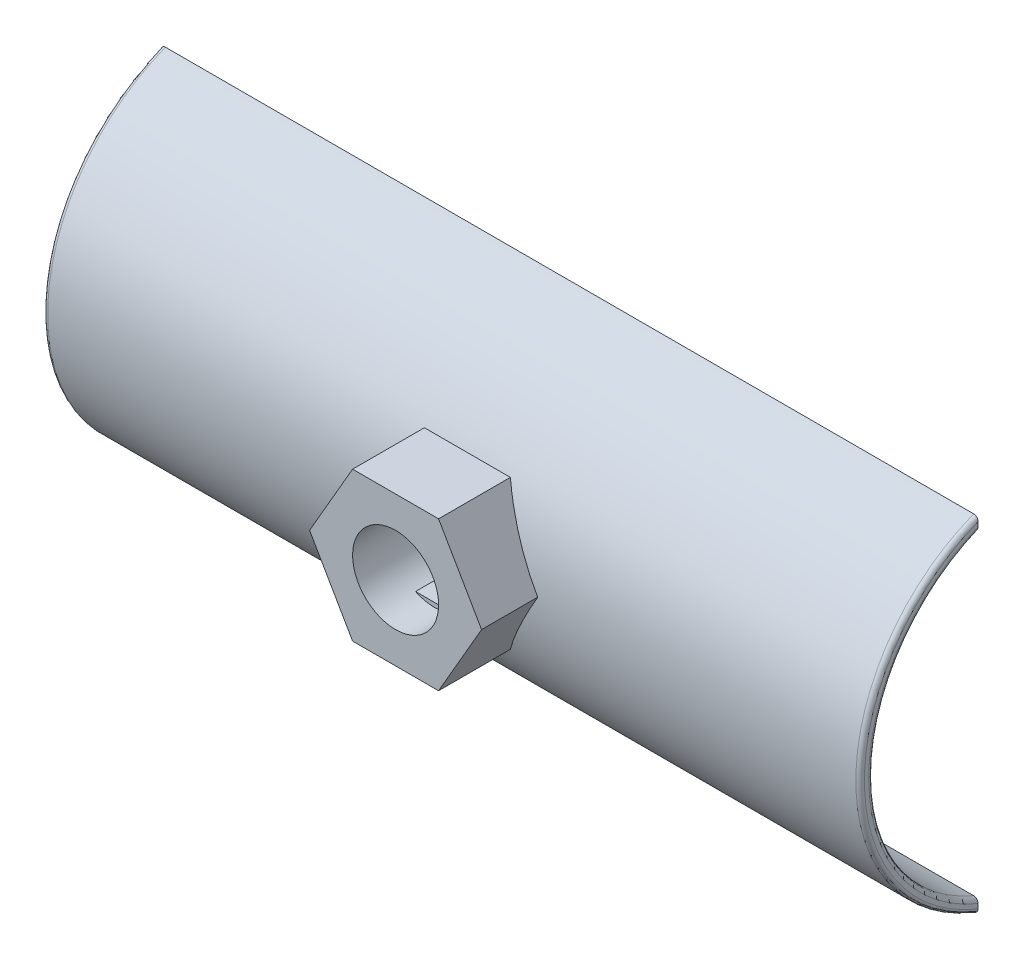
SolidWorks part; units mm, degrees
ref_plane "Front Plane" through (0, 0, 0) normal (0, 0, 1) x (1, 0, 0)
ref_plane "Top Plane" through (0, 0, 0) normal (0, 1, 0) x (1, 0, 0)
ref_plane "Right Plane" through (0, 0, 0) normal (1, 0, 0) x (0, 0, -1)
sketch "Sketch1" plane through (0, 0, 0) normal (0, 0, 1) x (1, 0, 0)
  line L0 (10, -17.3205) -> (20, 0)
  line L1 (20, 0) -> (10, 17.3205)
  line L2 (10, 17.3205) -> (-10, 17.3205)
  line L3 (-10, 17.3205) -> (-20, 0)
  line L4 (-20, 0) -> (-10, -17.3205)
  line L5 (-10, -17.3205) -> (10, -17.3205)
  circle A0 centre (0, 0) radius 17.3205 construction
  dimension "D1" = 20
extrude "Boss-Extrude1" add sketch "Sketch1" along normal blind 20
sketch "Sketch3" plane through (0, 0, 0) normal (0, 0, -1) x (-1, 0, 0)
  line L0 (0, 0) -> (0, 10) construction
  line L1 (0, 0) -> (10, 0) construction
  line L2 (-4.3589, 9) -> (4.3589, 9)
  line L3 (-4.3589, -9) -> (4.3589, -9)
  circle A0 centre (0, 0) radius 10
  dimension "D1" = 9
extrude "Cut-Extrude1" cut sketch "Sketch3" against normal blind 11 contours L2 A0 L3 region at (0, 0, 0)
sketch "Sketch4" plane through (0, 0, 11) normal (0, 0, -1) x (-1, 0, 0)
  circle A0 centre (0, 0) radius 10
extrude "Cut-Extrude2" cut sketch "Sketch4" against normal blind 11
sketch "Sketch5" plane through (0, 0, 0) normal (1, 0, 0) x (0, 0, -1)
  line L0 (0, 0) -> (76.0555, 0) construction
  line L2 (-20, -17.3205) -> (0, -17.3205) construction
  line L5 (20.4789, 40.0795) -> (20.4789, 36.8425)
  line L6 (20.4789, -36.8425) -> (20.4789, -40.0795)
  arc A2 (20.4789, 36.8425) -> (20.4789, -36.8425) centre (36.0555, 0) ccw
  arc A3 (20.4789, 40.0795) -> (20.4789, -40.0795) centre (36.0555, 0) ccw
extrude "Boss-Extrude2" add sketch "Sketch5" along normal blind 95 and the other way blind 95
sketch "Sketch6" plane through (95, 0, 0) normal (1, 0, 0) x (0, 0, -1)
  circle A0 centre (36.0555, 0) radius 40
extrude "Cut-Extrude3" cut sketch "Sketch6" against normal through all
sketch "Sketch7" plane through (0, 0, 11) normal (0, 0, 1) x (1, 0, 0)
  line L1 (-4.3589, 9) -> (4.3589, 9)
  line L2 (-4.3589, 9) -> (4.3589, 9)
  line L3 (4.3589, -9) -> (-4.3589, -9)
  line L4 (4.3589, -9) -> (-4.3589, -9)
  circle A0 centre (0, 0) radius 10 construction
  arc A1 (4.3589, 9) -> (-4.3589, 9) centre (0, 0) ccw
  arc A3 (-4.3589, -9) -> (4.3589, -9) centre (0, 0) ccw
  arc A5 (-4.3589, 9) -> (-4.3589, -9) centre (0, 0) ccw
  arc A6 (4.3589, -9) -> (4.3589, 9) centre (0, 0) ccw
  dimension "D1" = 0
  dimension "D2" = 0
extrude "Cut-Extrude4" cut sketch "Sketch7" against normal through all
fillet "Fillet1" radius 1 4 edges at (-95, 0, 6.9445) (-95, 0, 3.9445) (95, 0, 6.9445) (95, 0, 3.9445)
